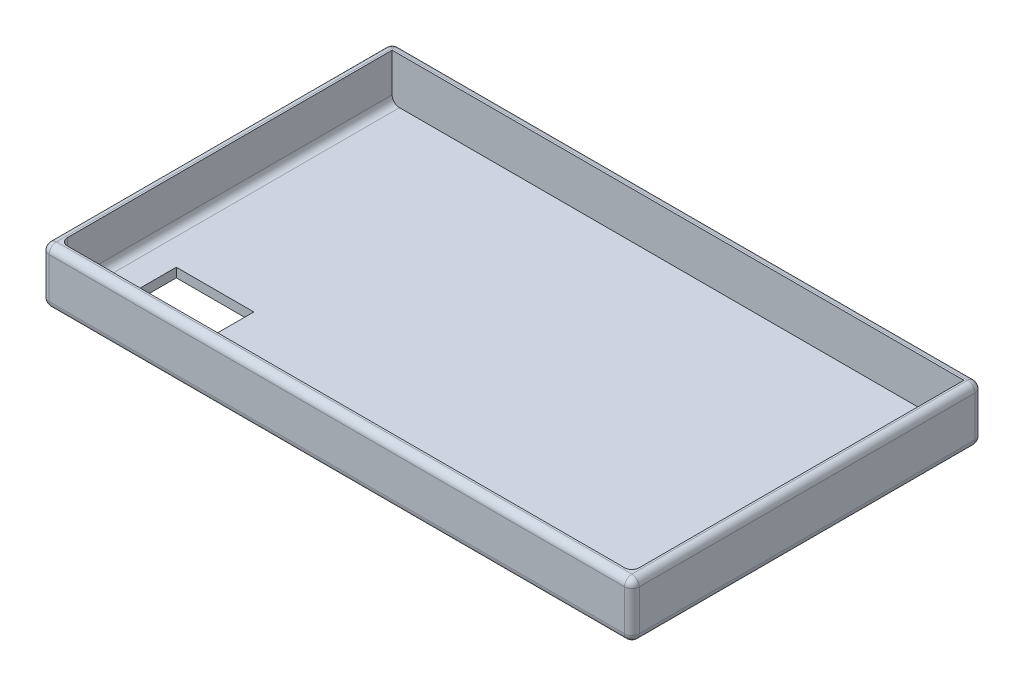
SolidWorks part; units mm, degrees
ref_plane "Front Plane" through (0, 0, 0) normal (0, 0, 1) x (1, 0, 0)
ref_plane "Top Plane" through (0, 0, 0) normal (0, 1, 0) x (1, 0, 0)
ref_plane "Right Plane" through (0, 0, 0) normal (1, 0, 0) x (0, 0, -1)
sketch "Sketch1" plane through (0, 0, 0) normal (0, 1, 0) x (1, 0, 0)
  line L1 (-74.314, 44.4298) -> (85.686, 44.4298)
  line L2 (-74.314, 44.4298) -> (-74.314, -50.5702)
  line L3 (-74.314, -50.5702) -> (85.686, -50.5702)
  line L4 (85.686, 44.4298) -> (85.686, -50.5702)
  dimension "D1" = 160
  dimension "D2" = 95
extrude "Boss-Extrude1" add sketch "Sketch1" along normal blind 15
shell "Shell1" thickness 2.5 removed face at (5.686, 15, 3.0702)
sketch "Sketch2" plane through (0, 0, 0) normal (0, 1, 0) x (1, 0, 0)
  line L1 (-62.6038, -25.777) -> (-41.6038, -25.777)
  line L2 (-62.6038, -25.777) -> (-62.6038, -38.777)
  line L3 (-62.6038, -38.777) -> (-41.6038, -38.777)
  line L4 (-41.6038, -25.777) -> (-41.6038, -38.777)
  dimension "D1" = 21
  dimension "D2" = 13
extrude "Cut-Extrude1" cut sketch "Sketch2" along normal blind 15
fillet "Fillet2" radius 2 9 edges at (-74.314, 7.5, 50.5702) (5.686, 0, 50.5702) (-74.314, 15, 3.0702) (-74.314, 0, 3.0702) (-74.314, 7.5, -44.4298) (5.686, 15, -44.4298) (85.686, 7.5, -44.4298) (5.686, 0, -44.4298) (85.686, 0, 3.0702)
fillet "Fillet8" radius 2 7 edges at (-73.7283, 14.4142, 49.9845) (85.1002, 0.5858, 49.9845) (85.1002, 14.4142, -43.844) (-71.814, 2.5, 3.0702) (6.686, 15, 50.5702) (85.686, 8.5, 50.5702) (85.686, 15, 4.0702)
fillet "Fillet13" radius 2 5 edges at (-71.814, 9.75, 48.0702) (-71.2283, 3.0858, 48.0702) (83.186, 8.75, 48.0702) (83.186, 2.5, 3.0702) (6.686, 2.5, 48.0702)
